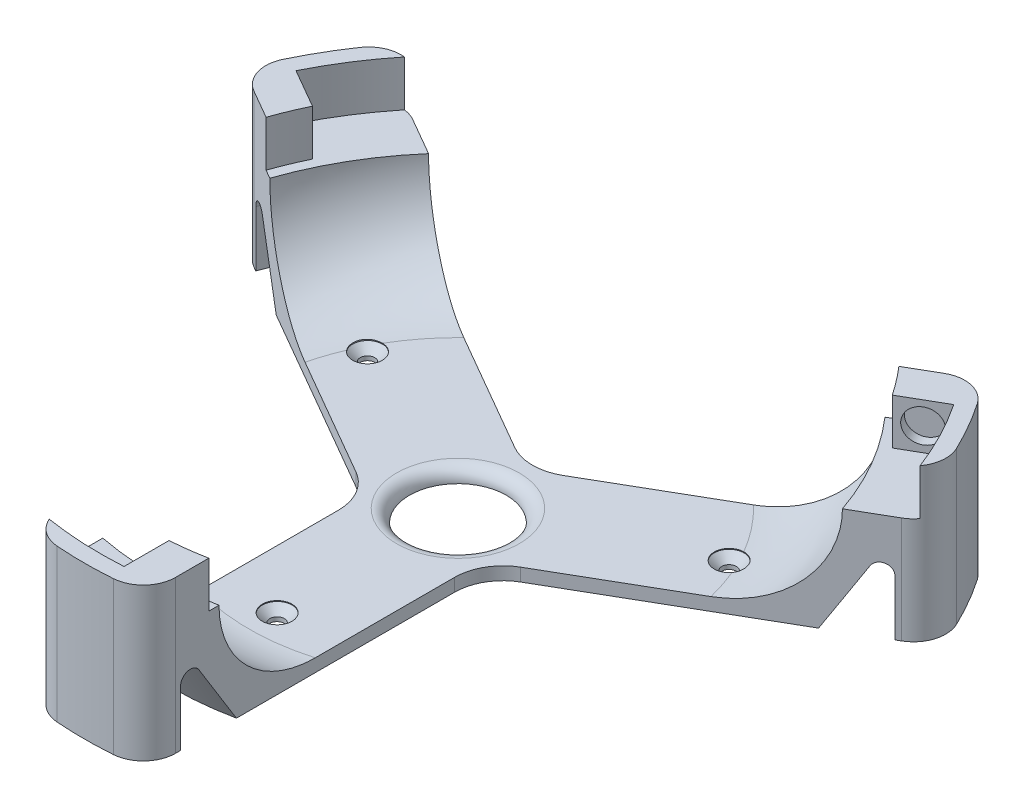
SolidWorks part; units mm, degrees
ref_plane "Front Plane" through (0, 0, 0) normal (0, 0, 1) x (1, 0, 0)
ref_plane "Top Plane" through (0, 0, 0) normal (0, 1, 0) x (1, 0, 0)
ref_plane "Right Plane" through (0, 0, 0) normal (1, 0, 0) x (0, 0, -1)
sketch "Sketch1" plane through (0, 0, 0) normal (0, 1, 0) x (1, 0, 0)
  line L0 (-56, 0) -> (-56, 28)
  line L1 (-28, 0) -> (-28, 28)
  line L3 (-28, 0) -> (-28, 28)
  line L4 (28, 0) -> (28, 28)
  line L5 (28, 0) -> (28, 28)
  line L7 (56, 0) -> (56, 28)
  line L8 (0, 0) -> (0, 28)
  line L9 (56, 0) -> (56, 28)
  line L10 (-56, 28) -> (-56, 56)
  line L11 (-56, 56) -> (-28, 56)
  line L12 (-28, 28) -> (-28, 56)
  line L13 (-28, 28) -> (-28, 56)
  line L15 (0, 56) -> (28, 56)
  line L16 (28, 28) -> (28, 56)
  line L17 (28, 28) -> (28, 56)
  line L18 (28, 56) -> (56, 56)
  line L19 (56, 28) -> (56, 56)
  line L20 (-28, 56) -> (0, 56)
  line L21 (56, 28) -> (56, 56)
  line L23 (0, 28) -> (0, 56)
  line L24 (-56, -28) -> (-56, 0)
  line L25 (-28, -28) -> (-28, 0)
  line L27 (-28, -28) -> (-28, 0)
  line L28 (28, -28) -> (28, 0)
  line L29 (28, -28) -> (28, 0)
  line L31 (56, -28) -> (56, 0)
  line L32 (0, -28) -> (0, 0)
  line L33 (56, -28) -> (56, 0)
  line L34 (-56, 0) -> (-56, 28)
  line L35 (-56, 28) -> (-28, 28)
  line L36 (-28, 0) -> (-28, 28)
  line L37 (-28, 0) -> (-28, 28)
  line L38 (0, 0) -> (0, 28)
  line L39 (0, 28) -> (28, 28)
  line L40 (28, 0) -> (28, 28)
  line L41 (28, 0) -> (28, 28)
  line L42 (28, 28) -> (56, 28)
  line L43 (56, 0) -> (56, 28)
  line L44 (-28, 28) -> (0, 28)
  line L45 (56, 0) -> (56, 28)
  line L46 (0, 0) -> (0, 28)
  line L47 (0, 0) -> (0, 28)
  line L48 (28, -56) -> (56, -56)
  line L49 (0, -56) -> (28, -56)
  line L51 (0, -28) -> (28, -28)
  line L52 (28, -56) -> (28, -28)
  line L53 (28, -56) -> (28, -28)
  line L54 (-28, -56) -> (0, -56)
  line L55 (56, -56) -> (56, -28)
  line L56 (-56, -56) -> (-28, -56)
  line L57 (56, -56) -> (56, -28)
  line L58 (-56, -56) -> (-56, -28)
  line L59 (-56, -28) -> (-28, -28)
  line L60 (28, -28) -> (56, -28)
  line L61 (0, -28) -> (28, -28)
  line L62 (0, -28) -> (0, 0)
  line L63 (0, 0) -> (28, 0)
  line L64 (28, -28) -> (28, 0)
  line L65 (28, -28) -> (28, 0)
  line L66 (28, 0) -> (56, 0)
  line L67 (56, -28) -> (56, 0)
  line L68 (-28, -56) -> (-28, -28)
  line L69 (56, -28) -> (56, 0)
  line L70 (-28, -56) -> (-28, -28)
  line L72 (84, 0) -> (84, 28)
  line L81 (0, -56) -> (0, -28)
  line L82 (-28, -28) -> (0, -28)
  line L83 (-56, -28) -> (-28, -28)
  line L84 (-56, -28) -> (-56, 0)
  line L85 (-56, 0) -> (-28, 0)
  line L86 (-28, -28) -> (-28, 0)
  line L87 (-28, -28) -> (-28, 0)
  line L88 (-28, 0) -> (0, 0)
  line L89 (0, -28) -> (0, 0)
  line L90 (0, -28) -> (0, 0)
  line L92 (0, -56) -> (0, -28)
  line L93 (0, -28) -> (0, 0)
  line L94 (0, 0) -> (0, 28)
  line L95 (0, 28) -> (0, 56)
  dimension "D3" = 3
  dimension "D4" = 2
  dimension "D5" = 3
  dimension "D6" = 2
sketch "Sketch2" plane through (0, 0, 0) normal (0, 1, 0) x (1, 0, 0)
  circle A0 centre (0, 0) radius 93.75
  circle A1 centre (0, 0) radius 115.75
  dimension "D1" = 187.5
  dimension "D2" = 22
extrude "Boss-Extrude1" add sketch "Sketch2" along normal blind 29
sketch "Sketch4" plane through (0, 0, 0) normal (0, 0, 1) x (1, 0, 0)
  line L2 (115.75, 29) -> (-115.75, 29) construction
  line L3 (-115.75, 0) -> (115.75, 0) construction
  line L4 (93.75, 29) -> (93.75, 0)
  line L5 (93.75, 0) -> (64.75, 0)
  ellipse E0 centre (64.75, 29) end of major axis (64.75, 0) minor radius 29 (64.75, 0) -> (93.75, 29) ccw
  dimension "D1" = 29
revolve "Revolve5" add sketch "Sketch4" angle 360 about axis through (0, 29, 0) along (0, -1, 0)
sketch "Sketch5" plane through (0, 0, 0) normal (0, -1, 0) x (1, 0, 0)
  circle A0 centre (0, 0) radius 115.75
  circle A1 centre (0, 0) radius 115.75 construction
extrude "Boss-Extrude2" add sketch "Sketch5" along normal blind 4
sketch "Sketch6" plane through (0, -4, 0) normal (0, -1, 0) x (1, 0, 0)
  line L0 (18, 10.3923) -> (18, 58.2838)
  line L1 (18, 58.2838) -> (18, 148.9161)
  line L2 (-18, 10.3923) -> (-18, 58.2838)
  line L3 (0, -20.7846) -> (41.4752, -44.7304)
  line L4 (18, 10.3923) -> (59.4752, -13.5534)
  line L5 (59.4752, -13.5534) -> (137.9651, -58.8696)
  line L6 (0, -20.7846) -> (-41.4752, -44.7304)
  line L7 (-18, 10.3923) -> (-59.4752, -13.5534)
  line L8 (41.4752, -44.7304) -> (119.9651, -90.0465)
  line L9 (-59.4752, -13.5534) -> (-137.9651, -58.8696)
  line L10 (-41.4752, -44.7304) -> (-119.9651, -90.0465)
  line L11 (-18, 58.2838) -> (-18, 148.9161)
  arc A0 (137.9651, -58.8696) -> (18, 148.9161) centre (0, 0) ccw
  arc A1 (-119.9651, -90.0465) -> (119.9651, -90.0465) centre (0, 0) ccw
  arc A2 (-18, 148.9161) -> (-137.9651, -58.8696) centre (0, 0) ccw
  dimension "D1" = 3
extrude "Cut-Extrude1" cut sketch "Sketch6" against normal through all
sketch "Sketch9" plane through (0, 0, 0) normal (0, 1, 0) x (1, 0, 0)
  circle A0 centre (0, -56) radius 4.6
  circle A1 centre (-56, 28) radius 4.6
  circle A2 centre (56, 28) radius 4.6
  dimension "D1" = 9.2
  dimension "D2" = 9.2
  dimension "D3" = 9.2
extrude "Cut-Extrude2" cut sketch "Sketch9" along normal blind 20 and the other way blind 0.25
sketch "Sketch15" plane through (0, 0, 0) normal (0, 1, 0) x (1, 0, 0)
  circle A0 centre (0, 0) radius 15
  dimension "D1" = 30
extrude "Cut-Extrude5" cut sketch "Sketch15" against normal blind 12
fillet "Fillet1" radius 15 3 edges at (0, -2, -20.7846) (-18, -2, 10.3923) (18, -2, 10.3923)
fillet "Fillet2" radius 10 6 edges at (-90.023, 12.5, -72.7594) (-108.023, 12.5, -41.5825) (18, 12.5, 114.3419) (-18, 12.5, 114.3419) (108.023, 12.5, -41.5825) (90.023, 12.5, -72.7594)
fillet "Fillet4" radius 4 1 edges at (0, 0, 15)
hole_wizard "CSK for M4 Flat Head Machine Screw3" positions "3DSketch3" profile "Sketch14" countersink size "M4" standard "ANSI Metric" end condition through all
sketch3d "3DSketch3"
  line L0 (0, -0.25, 56) -> (0, 0, 56) construction
  line L1 (-56, -0.25, -28) -> (-56, 0, -28) construction
  line L2 (56, -0.25, -28) -> (56, 0, -28) construction
  point P0 (0, -0.25, 56)
  point P4 (-56, -0.25, -28)
  point P8 (56, -0.25, -28)
sketch "Sketch14" plane through (0, -0.25, 56) normal (1, 0, 0) x (0, 0, 1)
  line L0 (0, 0) -> (0, 3.75)
  line L1 (0, 3.75) -> (2.25, 3.75)
  line L2 (2.25, 3.75) -> (2.25, 2.45)
  line L3 (2.25, 2.45) -> (4.7, 0)
  line L5 (4.7, 0) -> (0, 0)
  line L6 (-2.25, 2.45) -> (-4.7, 0) construction
  line L11 (0, -6.35) -> (0, 107.95) construction
  dimension "Thru Hole Dia." = 4.5
  dimension "Thru Hole Depth" = 3.75
  dimension "Near C'Sink Dia." = 9.4
  dimension "Near C'Sink Angle" = 90
sketch "Sketch16" plane through (0, 29, 0) normal (0, 1, 0) x (1, 0, 0)
  line L0 (0, 0) -> (-100.2424, 57.875) construction
  line L1 (-106.9704, 36.2219) -> (-84.8543, 74.5281) construction
  line L2 (-91.4132, 31.9928) -> (-100.3198, 37.135)
  line L3 (-99.265, 49.1123) -> (-87.1989, 42.1459)
  line L5 (-70.6793, 61.5913) -> (-82.3198, 68.3119)
  line L6 (-100.3198, 37.135) -> (-88.6793, 30.4144)
  arc A0 (-100.3198, 37.135) -> (-103.3419, 39.8249) centre (-95.3198, 45.7953) cw
  arc A3 (-95.5769, 65.2925) -> (-104.3334, 50.1258) centre (0, 0) ccw construction
  arc A4 (-99.265, 49.1123) -> (-86.1603, 69.5842) centre (0, 0) cw
  arc A5 (-91.4132, 31.9928) -> (-87.1989, 42.1459) centre (0, 0) cw
  arc A8 (-82.3198, 68.3119) -> (-95.5769, 65.2925) centre (-87.3198, 59.6517) ccw
  arc A9 (-95.5769, 65.2925) -> (-104.3334, 50.1258) centre (0, 0) ccw
  arc A10 (-104.3334, 50.1258) -> (-100.3198, 37.135) centre (-95.3198, 45.7953) ccw
  arc A11 (-70.6793, 61.5913) -> (-88.6793, 30.4144) centre (0, 0) ccw
  arc A12 (-86.1603, 69.5842) -> (-95.5769, 65.2925) centre (-87.3198, 59.6517) ccw
  arc A13 (-95.5769, 65.2925) -> (-104.3334, 50.1258) centre (0, 0) ccw
  arc A14 (-104.3334, 50.1258) -> (-103.3419, 39.8249) centre (-95.3198, 45.7953) ccw
  point P14 (-95.9123, 55.375)
  dimension "D4" = 0
extrude "Boss-Extrude4" add sketch "Sketch16" along normal blind 14.2
sketch "Sketch20" plane through (-3.55, 0, 6.1488) normal (0.5, 0, -0.866) x (-0.866, 0, -0.5)
  line L0 (96.5894, 43.2) -> (110.5222, 43.2) construction
  line L1 (96.5894, 43.2) -> (96.5894, 29) construction
  circle A0 centre (103.5894, 36.2) radius 5.1
  dimension "D1" = 10.2
  dimension "D2" = 7
  dimension "D3" = 7
extrude "Cut-Extrude9" cut sketch "Sketch20" against normal blind 3.1
pattern_circular "CirPattern1" count 3 over 360 about axis through (0, 29, 0) along (0, -1, 0) of "Boss-Extrude4", "Cut-Extrude9"
ref_plane "Plane1" through (0, 0, 0) normal (0.5, 0, -0.866) x (-0.866, 0, -0.5)
sketch "Sketch22" plane through (0, 0, 0) normal (0.5, 0, -0.866) x (-0.866, 0, -0.5)
  line L0 (105.447, -4) -> (105.447, 24)
  line L1 (105.447, 43.2) -> (105.447, -4) construction
  line L2 (105.447, 24) -> (88.447, -4)
  line L3 (105.447, -4) -> (19.0526, -4) construction
  line L4 (88.447, -4) -> (105.447, -4)
  dimension "D1" = 28
  dimension "D2" = 17
revolve "Cut-Revolve1" cut sketch "Sketch22" angle 360 about axis through (0, 29, 0) along (0, -1, 0)
fillet "Fillet5" radius 3 3 edges at (91.3198, 24, -52.7235) (0, 24, 105.447) (-91.3198, 24, -52.7235)
